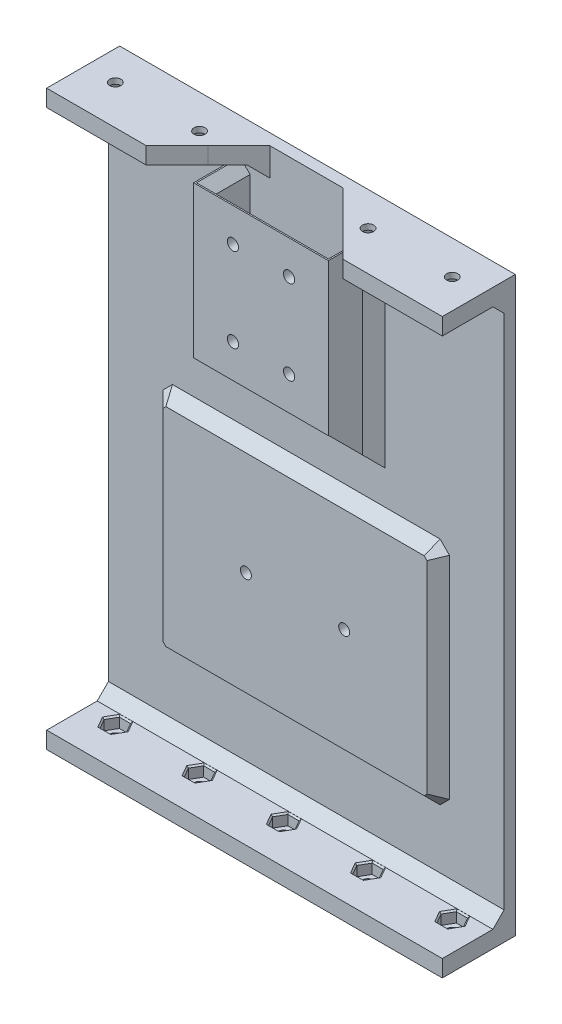
SolidWorks part; units mm, degrees
ref_plane "Front Plane" through (0, 0, 0) normal (0, 0, 1) x (1, 0, 0)
ref_plane "Top Plane" through (0, 0, 0) normal (0, 1, 0) x (1, 0, 0)
ref_plane "Right Plane" through (0, 0, 0) normal (1, 0, 0) x (0, 0, -1)
sketch "Sketch1" plane through (0, 0, 0) normal (0, 0, 1) x (1, 0, 0)
  line L1 (-70.45, -102) -> (70.45, -102)
  line L2 (-70.45, -102) -> (-70.45, 102)
  line L3 (-70.45, 102) -> (70.45, 102)
  line L4 (70.45, -102) -> (70.45, 102)
  line L5 (-70.45, -102) -> (70.45, 102) construction
  line L6 (-70.45, 102) -> (70.45, -102) construction
  point P0 (0, 0)
  dimension "D1" = 140.9
  dimension "D2" = 204
extrude "Boss-Extrude1" add sketch "Sketch1" against normal blind 4
sketch "Sketch2" plane through (0, 0, 0) normal (0, 0, 1) x (1, 0, 0)
  line L0 (70.45, 102) -> (-70.45, 102) construction
  line L1 (-24, 93.1) -> (24, 93.1)
  line L2 (-24, 93.1) -> (-24, 39.1)
  line L3 (-24, 39.1) -> (24, 39.1)
  line L4 (24, 93.1) -> (24, 39.1)
  line L5 (-24, 93.1) -> (24, 39.1) construction
  line L6 (-24, 39.1) -> (24, 93.1) construction
  point P0 (0, 66.1)
  dimension "D1" = 48
  dimension "D2" = 54
  dimension "D3" = 8.9
extrude "Boss-Extrude2" add sketch "Sketch2" along normal blind 16.12
sketch "Sketch4" plane through (0, 0, 0) normal (0, 0, 1) x (1, 0, 0)
  line L0 (70.45, -102) -> (70.45, 102) construction
  line L1 (-70.45, 102) -> (70.45, 102)
  line L2 (-70.45, 102) -> (-70.45, 96)
  line L3 (-70.45, 96) -> (70.45, 96)
  line L4 (70.45, 102) -> (70.45, 96)
  line L6 (-70.45, -102) -> (70.45, -102)
  line L7 (-70.45, -102) -> (-70.45, -96)
  line L8 (-70.45, -96) -> (70.45, -96)
  line L9 (70.45, -102) -> (70.45, -96)
  dimension "D1" = 6
  dimension "D2" = 6
extrude "Boss-Extrude3" add sketch "Sketch4" along normal blind 22
sketch "Sketch5" plane through (0, 102, 0) normal (0, 1, 0) x (1, 0, 0)
  line L0 (-999.5545, -8) -> (49000.4455, -8) construction
  line L1 (70.45, 4) -> (-70.45, 4) construction
  line L2 (0, -55) -> (0, 55) construction
  circle A0 centre (-30, -8) radius 2
  circle A1 centre (-60, -8) radius 2
  circle A4 centre (60, -8) radius 2
  circle A5 centre (30, -8) radius 2
  dimension "D2" = 4
  dimension "D1" = 12
  dimension "D3" = 30
  dimension "D4" = 60
extrude "Cut-Extrude1" cut sketch "Sketch5" against normal through all both and the other way through all
sketch "Sketch6" plane through (0, 102, 0) normal (0, 1, 0) x (1, 0, 0)
  line L0 (70.45, -22) -> (-70.45, -22) construction
  line L1 (-24, -16.12) -> (-24, 0) construction
  line L2 (24, -16.12) -> (24, 0) construction
  line L4 (24, 0) -> (-24, 0)
  line L5 (-24, 0) -> (-24, -16.12)
  line L6 (-24, -16.12) -> (24, -16.12)
  line L7 (24, -16.12) -> (24, 0)
  line L8 (24, 0) -> (-24, 0)
  line L9 (-24, 0) -> (-24, -22)
  line L10 (-24, -22) -> (24, -22)
  line L11 (24, -22) -> (24, 0)
  dimension "D1" = 0
extrude "Cut-Extrude2" cut sketch "Sketch6" against normal up to next
chamfer "Chamfer1" distance 11 angle 45 4 edges at (24, 99, 22) (24, 99, 0) (-24, 99, 0) (-24, 99, 22)
chamfer "Chamfer2" distance 16 angle 45 1 edges at (0, 39.1, 0)
shell "Shell1" thickness 4 removed face at (0, 93.1, 8.06)
sketch "Sketch7" plane through (0, 0, 16.12) normal (0, 0, 1) x (1, 0, 0)
  line L0 (0, -1000) -> (0, 49000) construction
  line L1 (24, 93.1) -> (-24, 93.1) construction
  line L2 (-10, 81.1) -> (10, 81.1) construction
  line L3 (-10, 81.1) -> (-10, 51.1) construction
  circle A0 centre (-10, 81.1) radius 2
  circle A1 centre (10, 81.1) radius 2
  circle A2 centre (10, 51.1) radius 2
  circle A3 centre (-10, 51.1) radius 2
  dimension "D3" = 4
  dimension "D1" = 10
  dimension "D2" = 12
  dimension "D6" = 20
  dimension "D7" = 30
  dimension "D4" = 2
  dimension "D5" = 2
extrude "Cut-Extrude3" cut sketch "Sketch7" against normal up to next
chamfer "Chamfer3" distance 3.5 angle 45 3 edges at (20, 93.1, 6.06) (0, 93.1, 12.12) (-20, 93.1, 6.06)
chamfer "Chamfer4" distance 4 angle 45 3 edges at (0, -96, 0) (41.725, 96, 0) (-41.725, 96, 0)
chamfer "Chamfer5" distance 4 angle 45 2 edges at (-24, 57.55, 0) (24, 57.55, 0)
sketch "Sketch8" plane through (0, -96, 0) normal (0, 1, 0) x (1, 0, 0)
  line L0 (-26.0163, -8) -> (-28.0081, -4.55)
  line L1 (-56.0163, -8) -> (-58.0081, -4.55)
  line L2 (-58.0081, -4.55) -> (-61.9919, -4.55)
  line L3 (-61.9919, -4.55) -> (-63.9837, -8)
  line L4 (-63.9837, -8) -> (-61.9919, -11.45)
  line L5 (-61.9919, -11.45) -> (-58.0081, -11.45)
  line L6 (-58.0081, -11.45) -> (-56.0163, -8)
  line L7 (-28.0081, -4.55) -> (-31.9919, -4.55)
  line L8 (-31.9919, -4.55) -> (-33.9837, -8)
  line L9 (-33.9837, -8) -> (-31.9919, -11.45)
  line L10 (-31.9919, -11.45) -> (-28.0081, -11.45)
  line L11 (-28.0081, -11.45) -> (-26.0163, -8)
  line L12 (3.9837, -8) -> (1.9919, -4.55) [skipped]
  line L13 (1.9919, -4.55) -> (-1.9919, -4.55) [skipped]
  line L14 (-1.9919, -4.55) -> (-3.9837, -8) [skipped]
  line L15 (-3.9837, -8) -> (-1.9919, -11.45) [skipped]
  line L16 (-1.9919, -11.45) -> (1.9919, -11.45) [skipped]
  line L17 (1.9919, -11.45) -> (3.9837, -8) [skipped]
  line L18 (33.9837, -8) -> (31.9919, -4.55)
  line L19 (31.9919, -4.55) -> (28.0081, -4.55)
  line L20 (28.0081, -4.55) -> (26.0163, -8)
  line L21 (26.0163, -8) -> (28.0081, -11.45)
  line L22 (28.0081, -11.45) -> (31.9919, -11.45)
  line L23 (31.9919, -11.45) -> (33.9837, -8)
  line L24 (63.9837, -8) -> (61.9919, -4.55)
  line L25 (61.9919, -4.55) -> (58.0081, -4.55)
  line L26 (58.0081, -4.55) -> (56.0163, -8)
  line L27 (56.0163, -8) -> (58.0081, -11.45)
  line L28 (58.0081, -11.45) -> (61.9919, -11.45)
  line L29 (61.9919, -11.45) -> (63.9837, -8)
  line L30 (-56.0163, -8) -> (-26.0163, -8) construction
  circle A0 centre (-60, -8) radius 3.45 construction
  dimension "D1" = 6.9
  dimension "D3" = 30
  dimension "D2" = 5
extrude "Cut-Extrude4" cut sketch "Sketch8" against normal blind 4
mirror "Mirror1" about plane through (0, 0, 0) normal (0, 1, 0) of "Cut-Extrude4"
sketch "Sketch9" plane through (0, 0, 0) normal (0, 0, 1) x (1, 0, 0)
  line L0 (-70.45, -92) -> (70.45, -92) construction
  line L1 (-47, 7) -> (47, 7)
  line L2 (-47, 7) -> (-47, -67)
  line L3 (-47, -67) -> (47, -67)
  line L4 (47, 7) -> (47, -67)
  line L5 (-47, -30) -> (47, -30) construction
  circle A2 centre (-17.5, -30) radius 1.95
  circle A3 centre (17.5, -30) radius 1.95
  point P4 (0, 7)
  point P14 (0, -67)
  dimension "D4" = 3.9
  dimension "D1" = 94
  dimension "D2" = 74
  dimension "D3" = 25
  dimension "D5" = 35
  dimension "D6" = 17.5
extrude "Boss-Extrude4" add sketch "Sketch9" along normal blind 4
sketch "Sketch10" plane through (0, 0, 4) normal (0, 0, 1) x (1, 0, 0)
  circle A0 centre (-17.5, -30) radius 1.95 construction
  circle A1 centre (-17.5, -30) radius 1.95
  circle A2 centre (17.5, -30) radius 1.95 construction
  circle A3 centre (17.5, -30) radius 1.95
extrude "Cut-Extrude5" cut sketch "Sketch10" against normal blind 5
chamfer "Chamfer7" distance 1 angle 45 4 edges at (47, 7, 2) (47, -67, 2) (-47, -67, 2) (-47, 7, 2)
chamfer "Chamfer8" distance 4 angle 45 8 edges at (-46.5, 6.5, 0) (-47, -30, 0) (-46.5, -66.5, 0) (0, -67, 0) (46.5, -66.5, 0) (47, -30, 0) (46.5, 6.5, 0) (0, 7, 0)
sketch "Sketch11" plane through (0, -96, 0) normal (0, 1, 0) x (1, 0, 0)
  line L0 (-70.45, 4) -> (70.45, 4) construction
  circle A0 centre (0, -8) radius 2
  dimension "D1" = 4
  dimension "D2" = 12
extrude "Cut-Extrude6" cut sketch "Sketch11" against normal up to next
sketch "Sketch12" plane through (0, -96, 0) normal (0, 1, 0) x (1, 0, 0)
  line L1 (1.9919, -4.55) -> (-1.9919, -4.55)
  line L2 (-1.9919, -4.55) -> (-3.9837, -8)
  line L3 (-3.9837, -8) -> (-1.9919, -11.45)
  line L4 (-1.9919, -11.45) -> (1.9919, -11.45)
  line L5 (1.9919, -11.45) -> (3.9837, -8)
  line L6 (3.9837, -8) -> (1.9919, -4.55)
  circle A0 centre (0, -8) radius 3.45 construction
  circle A1 centre (0, -8) radius 2 construction
  dimension "D1" = 6.9
extrude "Cut-Extrude7" cut sketch "Sketch12" against normal up to surface (4 mm away) up to face at (-30, -100, 8)
chamfer "Chamfer9" distance 0.5 angle 45 54 edges at (60, -96, 4.55) (57.0122, -96, 6.275) (57.0122, -96, 9.725) (60, -96, 11.45) (62.9878, -96, 9.725) (62.9878, -96, 6.275) (30, -96, 4.55) (27.0122, -96, 6.275) (27.0122, -96, 9.725) (30, -96, 11.45) (32.9878, -96, 9.725) (32.9878, -96, 6.275) (-2.9878, -96, 6.275) (-2.9878, -96, 9.725) (0, -96, 11.45) (2.9878, -96, 9.725) (2.9878, -96, 6.275) (0, -96, 4.55) (-30, -96, 4.55) (-32.9878, -96, 6.275) (-32.9878, -96, 9.725) (-30, -96, 11.45) (-27.0122, -96, 9.725) (-27.0122, -96, 6.275) (-60, -96, 4.55) (-62.9878, -96, 6.275) (-62.9878, -96, 9.725) (-60, -96, 11.45) (-57.0122, -96, 9.725) (-57.0122, -96, 6.275) (60, 96, 11.45) (57.0122, 96, 9.725) (57.0122, 96, 6.275) (60, 96, 4.55) (62.9878, 96, 6.275) (62.9878, 96, 9.725) (30, 96, 11.45) (27.0122, 96, 9.725) (27.0122, 96, 6.275) (30, 96, 4.55) (32.9878, 96, 6.275) (32.9878, 96, 9.725) (-30, 96, 11.45) (-32.9878, 96, 9.725) (-32.9878, 96, 6.275) (-30, 96, 4.55) (-27.0122, 96, 6.275) (-27.0122, 96, 9.725) (-60, 96, 11.45) (-62.9878, 96, 9.725) (-62.9878, 96, 6.275) (-60, 96, 4.55) (-57.0122, 96, 6.275) (-57.0122, 96, 9.725)
